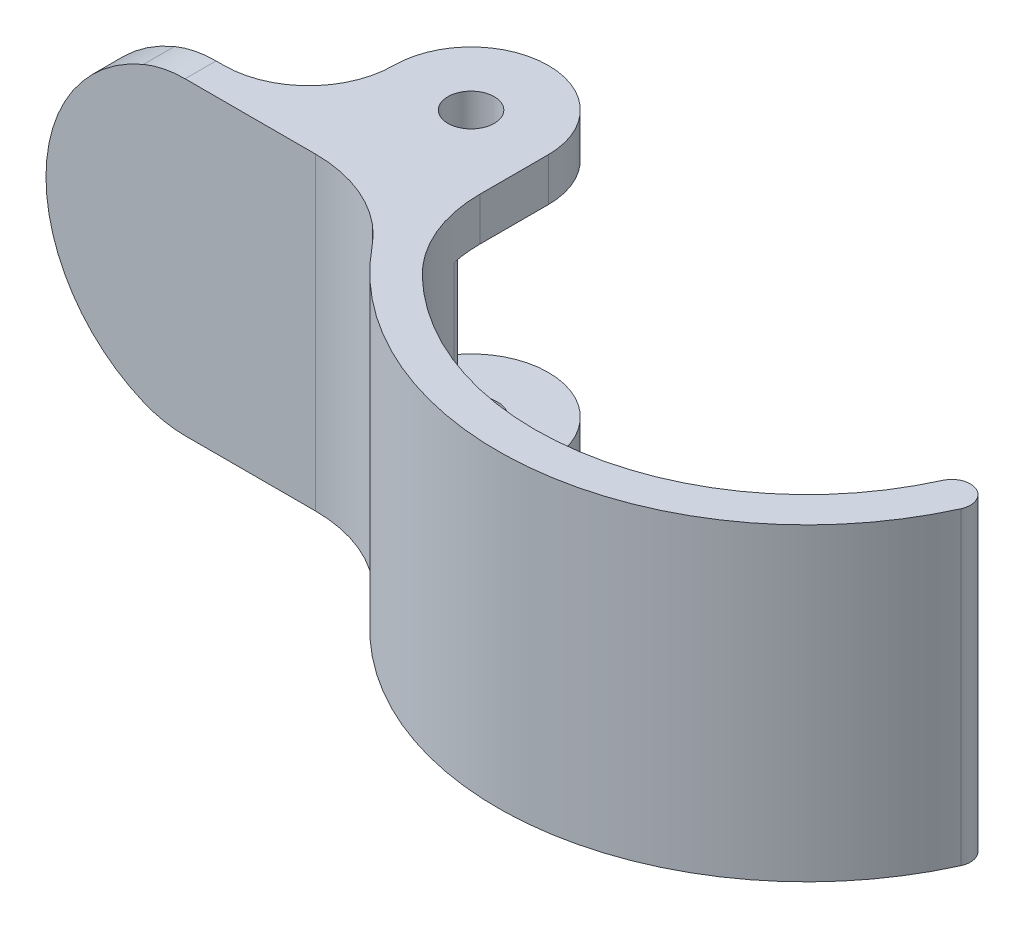
SolidWorks part; units mm, degrees
ref_plane "Front Plane" through (0, 0, 0) normal (0, 0, 1) x (1, 0, 0)
ref_plane "Top Plane" through (0, 0, 0) normal (0, 1, 0) x (1, 0, 0)
ref_plane "Right Plane" through (0, 0, 0) normal (1, 0, 0) x (0, 0, -1)
sketch "Sketch1" plane through (0, 0, 0) normal (0, 0, 1) x (1, 0, 0)
  line L0 (0, 10) -> (0, -10) construction
  line L1 (-12, -10) -> (5, -10)
  line L2 (-12, -10) -> (-12, 10)
  line L3 (-12, 10) -> (5, 10)
  line L4 (5, -10) -> (5, 10)
  point P6 (9.2355, -10)
  dimension "D1" = 20
  dimension "D2" = 12
  dimension "D3" = 5
extrude "Boss-Extrude1" add sketch "Sketch1" along normal blind 2
sketch "Sketch2" plane through (0, 10, 0) normal (0, 1, 0) x (1, 0, 0)
  line L0 (0, 0) -> (0, 5.5) construction
  line L1 (5, 0) -> (-5, 0)
  line L2 (5, 0) -> (-12, 0) construction
  line L3 (-5, 0) -> (-5, 5.5)
  line L4 (5, 0) -> (5, 5.5)
  line L5 (-5, 5.5) -> (5, 5.5) construction
  circle A0 centre (0, 5.5) radius 1.5
  arc A1 (-5, 5.5) -> (5, 5.5) centre (0, 5.5) cw
  point P8 (0, 0)
  point P10 (-5.3132, 0)
  point P12 (-5.1791, 5.7246)
  point P13 (-5.2983, 4.2652)
  dimension "D1" = 3
  dimension "D2" = 5
  dimension "D3" = 5.5
extrude "Boss-Extrude2" add sketch "Sketch2" against normal blind 2.8
fillet "Fillet1" radius 5.5 1 edges at (-5, 8.6, 0)
mirror "Mirror1" about plane through (0, 0, 0) normal (0, 1, 0) of "Fillet1", "Boss-Extrude2"
hole_wizard "CSK for M3 Countersunk Flat Head Screw1" positions "Sketch3" profile "Sketch4" countersink size "M3" standard "DIN"
sketch "Sketch3" plane through (0, -10, 0) normal (0, -1, 0) x (-1, 0, 0)
  point P0 (0, 5.5)
sketch "Sketch4" plane through (0, -10, -5.5) normal (1, 0, 0) x (0, 0, -1)
  line L0 (0, 0) -> (0, 8.0215)
  line L1 (0, 8.0215) -> (1.7, 7)
  line L2 (1.7, 7) -> (1.7, 1.45)
  line L3 (1.7, 1.45) -> (3.15, 0)
  line L5 (3.15, 0) -> (0, 0)
  line L6 (-1.7, 1.45) -> (-3.15, 0) construction
  line L10 (0, 8.0215) -> (-1.7, 7) construction
  line L11 (0, -6.35) -> (0, 107.95) construction
  dimension "Hole Dia." = 3.4
  dimension "Hole Depth" = 7
  dimension "Near C'Sink Dia." = 6.3
  dimension "Near C'Sink Angle" = 90
  dimension "Drill Angle" = 118
sketch "Sketch5" plane through (0, 0, 2) normal (0, 0, 1) x (1, 0, 0)
  line L0 (0, 0) -> (-20, 0) construction
  line L1 (-12, 10) -> (-12, -10)
  line L2 (5, 10) -> (-12, 10) construction
  line L3 (-12, -10) -> (5, -10) construction
  line L4 (-12, 10) -> (-12, -10) construction
  arc A0 (-12, -10) -> (-12, 10) centre (-9.75, 0) cw
  point P10 (-13.5, -10)
  dimension "D1" = 20
extrude "Boss-Extrude3" add sketch "Sketch5" against normal up to surface (2 mm away) up to face at (-7, 0, 0)
fillet "Fillet2" radius 7 2 edges at (-12, -10, 1) (-12, 10, 1)
sketch "Sketch6" plane through (0, 10, 0) normal (0, 1, 0) x (1, 0, 0)
  line L0 (0, 0) -> (36, 0) construction
  line L2 (2.2399, -2) -> (4.3672, -0.8888)
  line L3 (5, -2) -> (-11, -2) construction
  arc A0 (4.3672, -0.8888) -> (17.5794, -10.1774) centre (19.9671, 7.2599) ccw construction
  arc A1 (2.2399, -2) -> (38.1863, -0.99) centre (19.9671, 7.2599) ccw
  arc A2 (4.3672, -0.8888) -> (36, 0) centre (19.9671, 7.2599) ccw
  arc A3 (2.2399, -2) -> (17.2538, -12.5552) centre (19.9671, 7.2599) ccw construction
  arc A4 (36, 0) -> (38.1863, -0.99) centre (37.0932, -0.495) cw
  dimension "D2" = 2.4
  dimension "D3" = 20
  dimension "D4" = 36
extrude "Boss-Extrude4" add sketch "Sketch6" against normal up to surface (20 mm away) up to face at (0, -10, -8.65)
fillet "Fillet3" radius 9 1 edges at (5, 0, 2)
fillet "Fillet4" radius 9 1 edges at (2.2399, 0, 2)
fillet "Fillet5" radius 1 1 edges at (5.0635, 0, 0)
